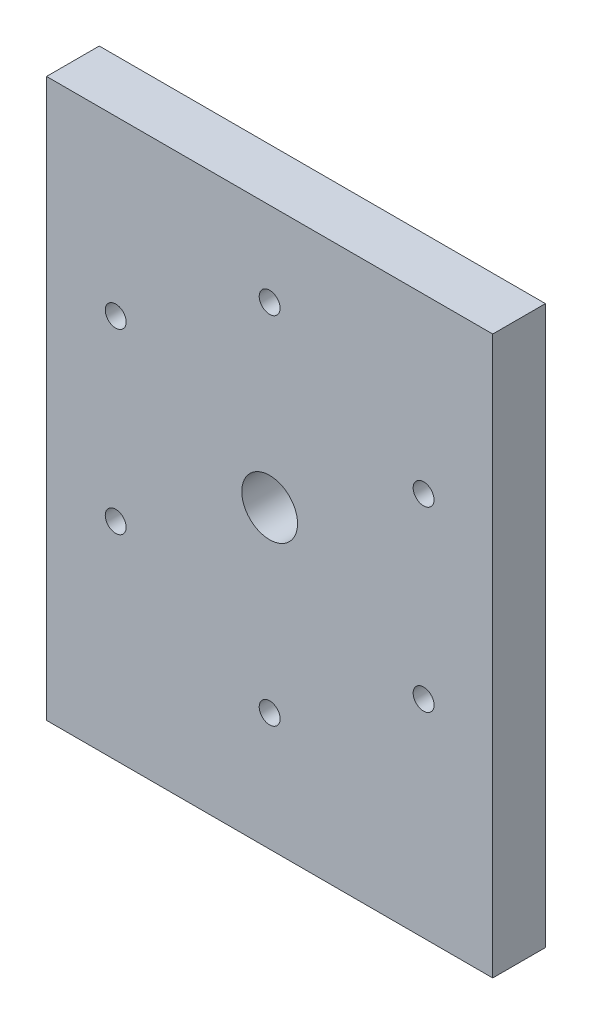
SolidWorks part; units mm, degrees
material "Acrylic (Medium-high impact)"
ref_plane "Front Plane" through (0, 0, 0) normal (0, 0, 1) x (1, 0, 0)
ref_plane "Top Plane" through (0, 0, 0) normal (0, 1, 0) x (1, 0, 0)
ref_plane "Right Plane" through (0, 0, 0) normal (1, 0, 0) x (0, 0, -1)
sketch "Sketch1" plane through (0, 0, 0) normal (0, 0, 1) x (1, 0, 0)
  line L0 (34.1802, 50.5429) -> (34.1802, 53.0508) construction
  line L1 (-50.8, 127) -> (50.8, 127)
  line L2 (-50.8, 127) -> (-50.8, 0)
  line L3 (-50.8, 0) -> (50.8, 0)
  line L4 (50.8, 127) -> (50.8, 0)
  circle A0 centre (0, 67.375) radius 6.35
  circle A7 centre (0, 67.375) radius 38.1 construction
  dimension "D1" = 127
  dimension "D3" = 12.7
  dimension "D12" = 76.2
  dimension "D2" = 101.6
  dimension "D5" = 67.375
extrude "Boss-Extrude1" add sketch "Sketch1" along normal blind 12
sketch "Sketch2" plane through (0, 0, 0) normal (0, 0, -1) x (-1, 0, 0)
  circle A0 centre (0, 107.8562) radius 2.3812
  circle A1 centre (0, 67.375) radius 38.1 construction
  dimension "D1" = 4.7625
extrude "Cut-Extrude1" cut sketch "Sketch2" against normal through all
pattern_circular "CirPattern1" count 6 every 60 about axis through (0, 67.375, 12) along (0, 0, -1) of "Cut-Extrude1"
sketch "Sketch3" plane through (0, 0, 0) normal (0, -1, 0) x (1, 0, 0)
  line L0 (31.75, 6) -> (-31.75, 6) construction
  line L2 (0, 0) -> (0, 12) construction
  line L3 (-50.8, 12) -> (50.8, 12) construction
  circle A0 centre (31.75, 6) radius 2.3812
  circle A1 centre (0, 6) radius 2.3813
  circle A2 centre (-31.75, 6) radius 2.3813
  point P9 (0, 6)
  dimension "D2" = 4.7625
  dimension "D1" = 31.75
extrude "Cut-Extrude2" cut sketch "Sketch3" against normal blind 19.05
